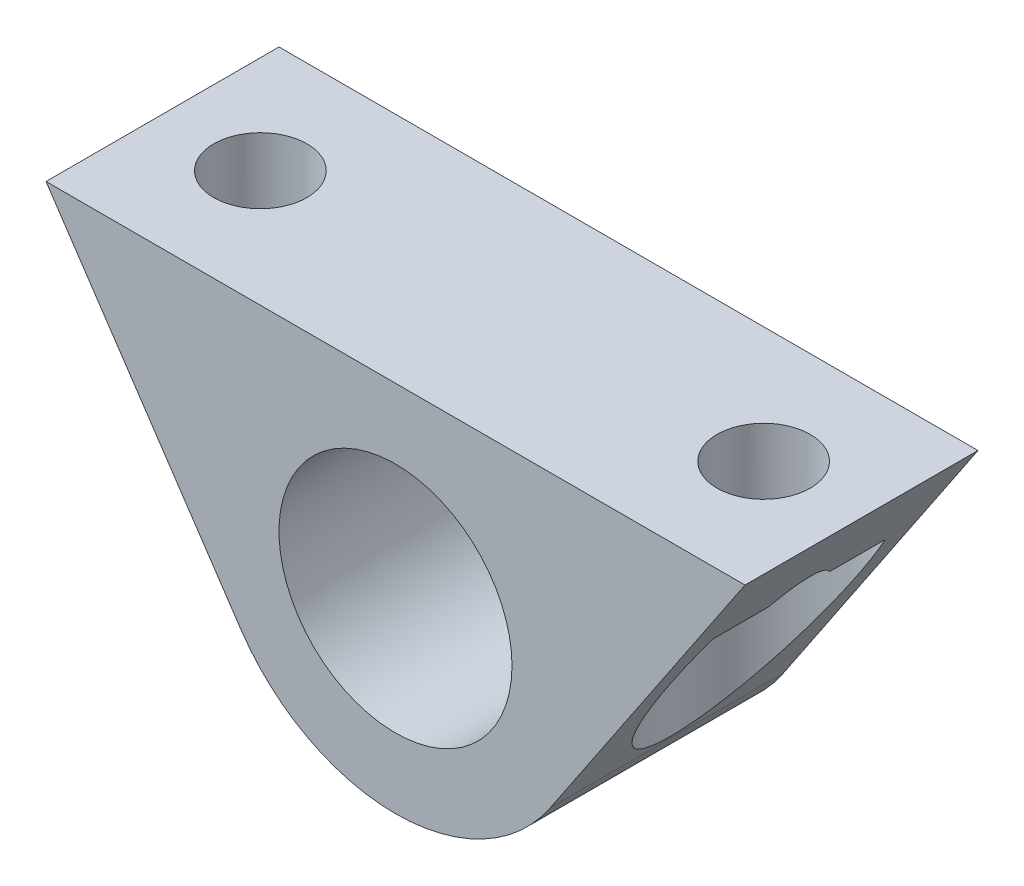
SolidWorks part; units mm, degrees
ref_plane "Front Plane" through (0, 0, 0) normal (0, 0, 1) x (1, 0, 0)
ref_plane "Top Plane" through (0, 0, 0) normal (0, 1, 0) x (1, 0, 0)
ref_plane "Right Plane" through (0, 0, 0) normal (1, 0, 0) x (0, 0, -1)
sketch "Sketch1" plane through (0, 0, 0) normal (0, 0, 1) x (1, 0, 0)
  line L0 (-7.5, 4) -> (7.5, 4)
  line L1 (0, -55) -> (0, 55) construction
  line L2 (-7.5, 4) -> (-3.3218, -2.2284)
  line L3 (7.5, 4) -> (3.3218, -2.2284)
  circle A0 centre (0, 0) radius 2.5
  arc A1 (-3.3218, -2.2284) -> (3.3218, -2.2284) centre (0, 0) ccw
  point P8 (0, 4)
  dimension "D1" = 5
  dimension "D2" = 8
  dimension "D3" = 15
extrude "Boss-Extrude1" add sketch "Sketch1" along normal blind 5
sketch "Sketch2" plane through (0, 4, 0) normal (0, 1, 0) x (1, 0, 0)
  line L0 (-7.5, -5) -> (-7.5, 0) construction
  line L1 (-7.5, -2.5) -> (-5.4, -2.5) construction
  line L2 (5.4, -2.5) -> (7.5, -2.5) construction
  line L3 (7.5, -5) -> (7.5, 0) construction
  circle A0 centre (-5.4, -2.5) radius 1
  circle A1 centre (5.4, -2.5) radius 1
  circle A2 centre (-5.4, -2.5) radius 2
  circle A3 centre (5.4, -2.5) radius 2
  point P10 (-7.5, -2.5)
  dimension "D1" = 2
  dimension "D2" = 4
  dimension "D3" = 2.1
extrude "Cut-Extrude1" cut sketch "Sketch2" against normal through all from offset 2 offset against normal yes
extrude "Cut-Extrude2" cut sketch "Sketch2<2>" against normal through all contours A0 | A1 region at (-5.4, 4, 2.5) region at (5.4, 4, 2.5)
sketch "Sketch2<2>" plane through (0, 4, 0) normal (0, 1, 0) x (1, 0, 0) same geometry as "Sketch2"
